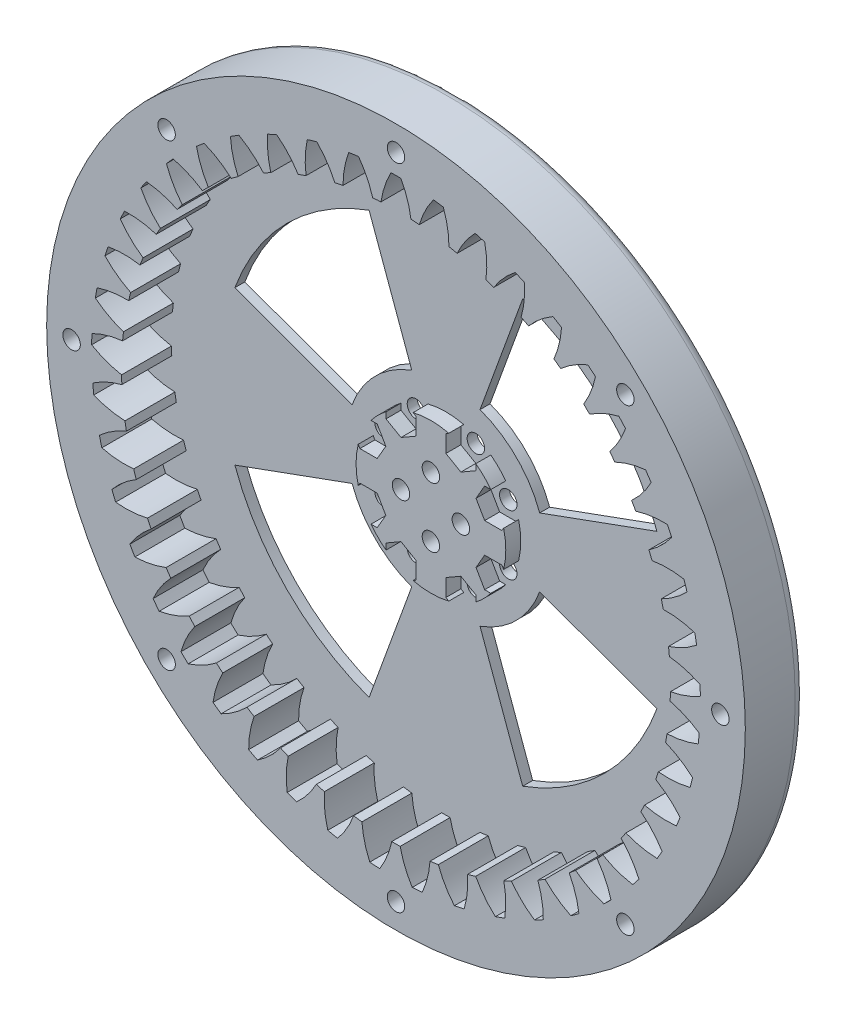
SolidWorks part; units mm, degrees
ref_plane "Front Plane" through (0, 0, 0) normal (0, 0, 1) x (1, 0, 0)
ref_plane "Top Plane" through (0, 0, 0) normal (0, 1, 0) x (1, 0, 0)
ref_plane "Right Plane" through (0, 0, 0) normal (1, 0, 0) x (0, 0, -1)
sketch "Sketch1" plane through (0, 0, 0) normal (0, 0, 1) x (1, 0, 0)
  circle A0 centre (0, 0) radius 55
  circle A1 centre (0, 0) radius 70
  dimension "D1" = 140
  dimension "D2" = 110
extrude "Boss-Extrude1" add sketch "Sketch1" along normal blind 10
sketch "Sketch2" plane through (0, 0, 10) normal (0, 0, 1) x (1, 0, 0)
  line L0 (0, 0) -> (0, 55) construction
  line L1 (0, 55) -> (0, 61) construction
  line L2 (-3, 54.9181) -> (3, 54.9181) construction
  line L3 (-1, 60.9918) -> (1, 60.9918) construction
  line L4 (-15, 52.357) -> (15, 52.357) construction
  circle A0 centre (0, 0) radius 55 construction
  arc A1 (1, 60.9918) -> (-1, 60.9918) centre (0, 0) ccw
  arc A2 (-3, 54.9181) -> (3, 54.9181) centre (0, 0) cw
  arc A5 (-1, 60.9918) -> (-3, 54.9181) centre (15, 52.357) ccw
  arc A6 (1, 60.9918) -> (3, 54.9181) centre (-15, 52.357) cw
  dimension "D1" = 2
  dimension "D2" = 6
  dimension "D3" = 30
  dimension "D4" = 6
extrude "Cut-Extrude1" cut sketch "Sketch2" against normal through all
pattern_circular "CirPattern1" count 45 every 8 about axis through (0, 0, 10) along (0, 0, 1) of "Cut-Extrude1"
sketch "Sketch4" plane through (0, 0, 0) normal (0, 0, -1) x (-1, 0, 0)
  circle A0 centre (0, 0) radius 70
extrude "Boss-Extrude2" add sketch "Sketch4" along normal blind 2
sketch "Sketch5" plane through (0, 0, -2) normal (0, 0, -1) x (-1, 0, 0)
  line L0 (6.8404, 18.7939) -> (15.3909, 42.2862)
  line L1 (18.7939, 6.8404) -> (42.2862, 15.3909)
  line L2 (0, 0) -> (54.2833, 0) construction
  line L3 (0, 0) -> (0, 54.2833) construction
  arc A0 (42.2862, 15.3909) -> (15.3909, 42.2862) centre (0, 0) ccw
  arc A1 (18.7939, 6.8404) -> (6.8404, 18.7939) centre (0, 0) ccw
  point P5 (51.0096, 18.566)
  dimension "D3" = 45
  dimension "D4" = 20
  dimension "D1" = 20
  dimension "D2" = 20
extrude "Cut-Extrude3" cut sketch "Sketch5" against normal through all
sketch "Sketch3" plane through (0, 0, 10) normal (0, 0, 1) x (1, 0, 0)
  line L0 (0, 70) -> (0, 65) construction
  circle A0 centre (0, 65) radius 1.75
  circle A1 centre (0, 0) radius 70 construction
  dimension "D2" = 3.5
  dimension "D1" = 5
extrude "Cut-Extrude2" cut sketch "Sketch3" against normal through all
pattern_circular "CirPattern2" count 8 every 45 about axis through (0, 0, 10) along (0, 0, 1) of "Cut-Extrude2"
sketch "Sketch7" plane through (0, 0, 0) normal (0, 0, 1) x (1, 0, 0)
  circle A0 centre (0, 0) radius 15
  dimension "D1" = 30
extrude "Boss-Extrude3" add sketch "Sketch7" along normal blind 3
sketch "Sketch6" plane through (0, 0, -2) normal (0, 0, -1) x (-1, 0, 0)
  line L0 (0, 0) -> (0, 6) construction
  circle A0 centre (0, 6) radius 1.75
  dimension "D1" = 3.5
  dimension "D2" = 6
extrude "Cut-Extrude4" cut sketch "Sketch6" against normal through all
pattern_circular "CirPattern3" count 4 every 90 about axis through (0, 0, 10) along (0, 0, 1) of "Cut-Extrude3", "Cut-Extrude4"
fillet "Fillet1" radius 2 1 edges at (-70, 0, -2)
sketch "Sketch8" plane through (0, 0, -2) normal (0, 0, -1) x (-1, 0, 0)
  line L0 (-12.5, 6) -> (12.5, 6) construction
  line L1 (12.5, 6) -> (12.5, -6) construction
  line L2 (12.5, -6) -> (-12.5, 6) construction
  line L3 (-12.5, 6) -> (-12.5, -6) construction
  line L4 (-12.5, -6) -> (12.5, -6) construction
  circle A0 centre (-12.5, 6) radius 1.75
  circle A1 centre (12.5, 6) radius 1.75
  circle A2 centre (12.5, -6) radius 1.75
  circle A3 centre (-12.5, -6) radius 1.75
  point P3 (0, 0)
  dimension "D1" = 3.5
  dimension "D3" = 3.5
  dimension "D4" = 3.5
  dimension "D5" = 3.5
  dimension "25" = 25
  dimension "D2" = 12
extrude "Cut-Extrude5" cut sketch "Sketch8" against normal through all
sketch "Sketch9" plane through (0, 0, 3) normal (0, 0, 1) x (1, 0, 0)
  line L1 (-10.7679, 3) -> (-9.0359, 6)
  line L2 (-9.0359, 6) -> (-10.7679, 9)
  line L3 (-10.7679, 9) -> (-14.2321, 9)
  line L4 (-14.2321, 9) -> (-15.9641, 6)
  line L5 (-15.9641, 6) -> (-14.2321, 3)
  line L6 (-14.2321, 3) -> (-10.7679, 3)
  line L7 (9.0359, 6) -> (10.7679, 3)
  line L8 (10.7679, 3) -> (14.2321, 3)
  line L9 (14.2321, 3) -> (15.9641, 6)
  line L10 (15.9641, 6) -> (14.2321, 9)
  line L11 (14.2321, 9) -> (10.7679, 9)
  line L12 (10.7679, 9) -> (9.0359, 6)
  line L13 (9.0359, -6) -> (10.7679, -9)
  line L14 (10.7679, -9) -> (14.2321, -9)
  line L15 (14.2321, -9) -> (15.9641, -6)
  line L16 (15.9641, -6) -> (14.2321, -3)
  line L17 (14.2321, -3) -> (10.7679, -3)
  line L18 (10.7679, -3) -> (9.0359, -6)
  line L19 (-9.0359, -6) -> (-10.7679, -3)
  line L20 (-10.7679, -3) -> (-14.2321, -3)
  line L21 (-14.2321, -3) -> (-15.9641, -6)
  line L22 (-15.9641, -6) -> (-14.2321, -9)
  line L23 (-14.2321, -9) -> (-10.7679, -9)
  line L24 (-10.7679, -9) -> (-9.0359, -6)
  circle A0 centre (-12.5, 6) radius 3 construction
  circle A1 centre (12.5, 6) radius 3 construction
  circle A2 centre (12.5, -6) radius 3 construction
  circle A3 centre (-12.5, -6) radius 3 construction
  point P28 (-7.5218, 6)
  dimension "D1" = 6
  dimension "D2" = 6
  dimension "D3" = 6
  dimension "D4" = 6
extrude "Cut-Extrude6" cut sketch "Sketch9" against normal blind 3
pattern_circular "CirPattern4" count 2 every 90 about axis through (0, 0, -2) along (0, 0, 1) of "Cut-Extrude6", "Cut-Extrude5"
